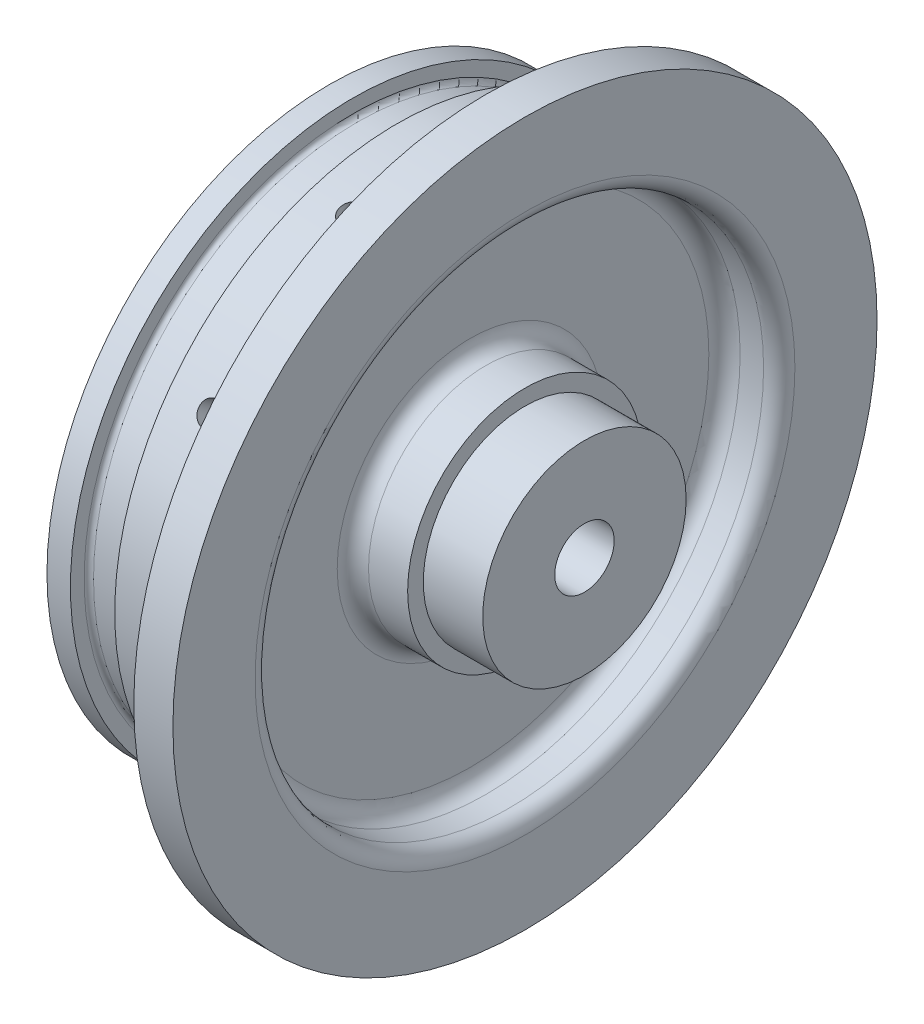
SolidWorks part; units mm, degrees
material "7075-T6 (SN)"
ref_plane "Front Plane" through (0, 0, 0) normal (0, 0, 1) x (1, 0, 0)
ref_plane "Top Plane" through (0, 0, 0) normal (0, 1, 0) x (1, 0, 0)
ref_plane "Right Plane" through (0, 0, 0) normal (1, 0, 0) x (0, 0, -1)
sketch "Sketch1" plane through (0, 0, 0) normal (1, 0, 0) x (0, 0, -1)
  circle A0 centre (0, 0) radius 57.15
  dimension "D1" = 114.3
extrude "Boss-Extrude1" add sketch "Sketch1" along normal blind 6.35
sketch "Sketch2" plane through (0, 0, 0) normal (-1, 0, 0) x (0, 0, 1)
  circle A0 centre (0, 0) radius 45.847
  dimension "D1" = 91.694
extrude "Boss-Extrude2" add sketch "Sketch2" along normal blind 25.4
sketch "Sketch10" plane through (0, 0, 0) normal (0, 1, 0) x (1, 0, 0)
  line L0 (0, 0) -> (-53.2238, 0) construction
  line L1 (-26.2636, 0) -> (26.2636, 0) construction
  line L2 (0, 0) -> (0, 64.5447) construction
  line L3 (0, -62.865) -> (0, 62.865) construction
ref_plane "Plane1" through (0, 0, -45.847) normal (0, 0, -1) x (-1, 0, 0)
sketch "Sketch11" plane through (0, 0, -45.847) normal (0, 0, -1) x (-1, 0, 0)
  line L0 (0, 0) -> (53.2238, 0) construction
  line L1 (0, -45.847) -> (0, 45.847) construction
  circle A0 centre (7.62, 0) radius 1.8986
  dimension "D2" = 3.7973
  dimension "D1" = 7.62
extrude "Cut-Extrude3" cut sketch "Sketch11" against normal blind 10.16
pattern_circular "CirPattern1" count 10 every 36 about axis through (0, 0, 0) along (-1, 0, 0) of "Cut-Extrude3" reverse direction yes
sketch "Sketch15" plane through (6.35, 0, 0) normal (1, 0, 0) x (0, 0, -1)
  circle A0 centre (0, 0) radius 4.826
  dimension "D1" = 9.652
extrude "Cut-Extrude4" cut sketch "Sketch15" against normal through all
sketch "Sketch16" plane through (0, 0, 0) normal (0, 0, 1) x (1, 0, 0)
  line L0 (0, 45.847) -> (-25.4, 45.847) construction
  line L1 (-21.59, 45.847) -> (-14.4018, 45.847)
  line L2 (-21.59, 45.847) -> (-21.59, 43.6245)
  line L3 (-20.828, 42.8625) -> (-15.1638, 42.8625)
  line L4 (-14.4018, 45.847) -> (-14.4018, 43.6245)
  line L5 (0, 0) -> (-53.2238, 0) construction
  line L6 (-25.4, 45.847) -> (-25.4, -45.847) construction
  arc A0 (-14.4018, 43.6245) -> (-15.1638, 42.8625) centre (-15.1638, 43.6245) cw
  arc A1 (-20.828, 42.8625) -> (-21.59, 43.6245) centre (-20.828, 43.6245) cw
  point P8 (-26.6119, 0)
  point P13 (-14.4018, 42.8625)
  point P16 (-21.59, 42.8625)
  dimension "D4" = 0.762
  dimension "D1" = 42.8625
  dimension "D2" = 3.81
  dimension "D3" = 7.1882
revolve "Cut-Revolve1" cut sketch "Sketch16" angle 360 about L0
sketch "Sketch17" plane through (6.35, 0, 0) normal (1, 0, 0) x (0, 0, -1)
  circle A0 centre (0, 0) radius 16.51
  circle A1 centre (0, 0) radius 4.826
  dimension "D1" = 33.02
extrude "Boss-Extrude3" add sketch "Sketch17" along normal blind 9.652
sketch "Sketch18" plane through (0, 0, 0) normal (0, 0, 1) x (1, 0, 0)
  line L0 (6.35, -57.15) -> (6.35, 57.15) construction
  line L1 (6.35, 41.275) -> (-2.54, 41.275)
  line L2 (6.35, 41.275) -> (6.35, 19.05)
  line L3 (6.35, 19.05) -> (-2.54, 19.05)
  line L4 (-2.54, 41.275) -> (-2.54, 19.05)
  line L5 (0, 0) -> (-53.2238, 0) construction
  dimension "D1" = 8.89
  dimension "D2" = 19.05
  dimension "D3" = 41.275
revolve "Cut-Revolve2" cut sketch "Sketch18" angle 360 about L0
fillet "Fillet1" radius 2.54 3 edges at (6.35, 0, -41.275) (-2.54, 0, -41.275) (-2.54, 0, -19.05)
